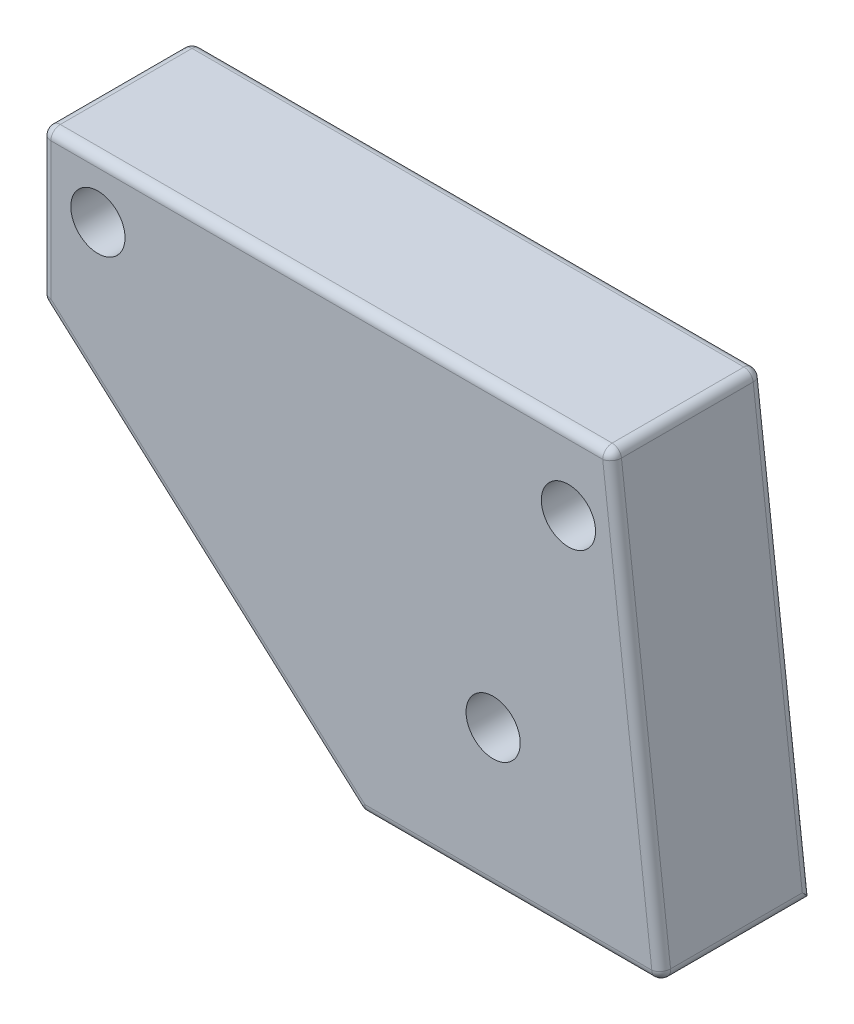
SolidWorks part; units mm, degrees
ref_plane "Front Plane" through (0, 0, 0) normal (0, 0, 1) x (1, 0, 0)
ref_plane "Top Plane" through (0, 0, 0) normal (0, 1, 0) x (1, 0, 0)
ref_plane "Right Plane" through (0, 0, 0) normal (1, 0, 0) x (0, 0, -1)
sketch "Sketch1" plane through (0, 0, 0) normal (0, 0, 1) x (1, 0, 0)
  line L1 (-25.4, 0) -> (0, 0)
  line L2 (0, 0) -> (-4.3265, 36.83)
  line L3 (-4.3265, 36.83) -> (-52.3748, 36.83)
  line L4 (328.6252, 36.83) -> (-52.3748, 36.83) construction
  line L5 (-52.3748, 36.83) -> (-52.3748, 24.13)
  line L6 (-52.3748, 36.83) -> (-52.3748, -7.62) construction
  line L7 (-52.3748, 24.13) -> (-25.4, 0)
  circle A0 centre (-47.6123, 32.0675) radius 2.286
  circle A1 centre (-7.9248, 30.48) radius 2.286
  circle A2 centre (-14.2748, 11.8269) radius 2.286
  point P8 (-4.3265, 36.83)
  dimension "D3" = 4.572
  dimension "D1" = 25.4
  dimension "D2" = 12.7
  dimension "D4" = 83.3
extrude "Boss-Extrude1" add sketch "Sketch1" along normal blind 12.7
sketch "Sketch3" plane through (0, 0, 0) normal (0, -1, 0) x (1, 0, 0)
  line L1 (0, 12.7) -> (0, 0) construction
  line L3 (-25.4, 0) -> (0, 0) construction
  circle A0 centre (-19.05, 6.35) radius 1.905
  circle A1 centre (-6.35, 6.35) radius 1.905
  dimension "D1" = 3.81
  dimension "D2" = 6.35
  dimension "D3" = 12.7
  dimension "D4" = 6.35
extrude "Cut-Extrude1" cut sketch "Sketch3" against normal blind 25.4
fillet "Fillet1" radius 0.7937 14 edges at (-52.3748, 30.48, 12.7) (-52.3748, 30.48, 0) (-52.3748, 24.13, 6.35) (-38.8874, 12.065, 12.7) (-25.4, 0, 6.35) (-38.8874, 12.065, 0) (0, 0, 6.35) (-2.1633, 18.415, 12.7) (-2.1633, 18.415, 0) (-4.3265, 36.83, 6.35) (-28.3507, 36.83, 12.7) (-52.3748, 36.83, 6.35) (-28.3507, 36.83, 0) (-12.7, 0, 12.7)
